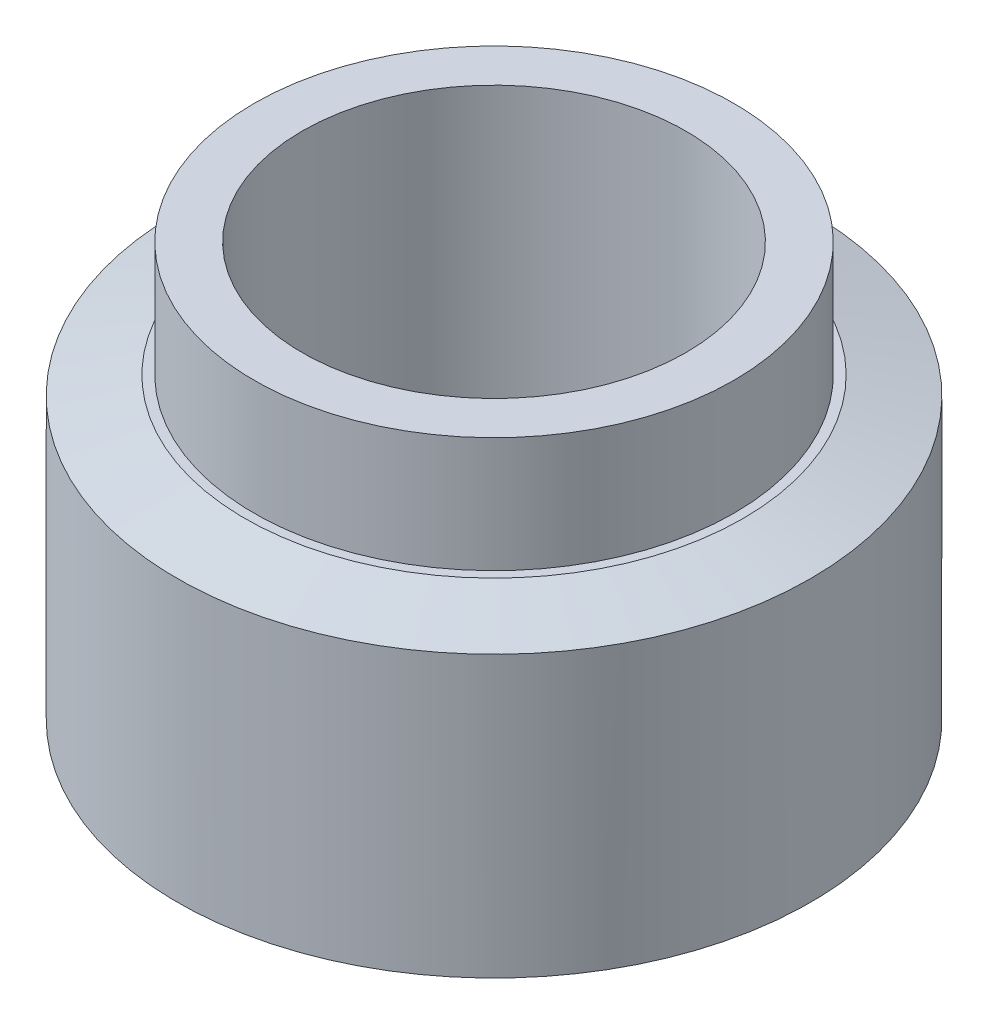
SolidWorks part; units mm, degrees
material "Сталь ШХ15 ГОСТ 801-78"
ref_plane "Plane1" through (0, 0, 0) normal (0, 0, 1) x (1, 0, 0)
ref_plane "Plane2" through (0, 0, 0) normal (0, 1, 0) x (1, 0, 0)
ref_plane "Plane3" through (0, 0, 0) normal (1, 0, 0) x (0, 0, -1)
sketch "Эскиз2" plane through (0, 0, 0) normal (0, 0, 1) x (1, 0, 0)
  line L0 (0, 0) -> (3.3, 0)
  line L1 (3.3, 0) -> (3.3, 3.3)
  line L2 (3.3, 3.3) -> (2.5, 3.3)
  line L3 (2.5, 3.3) -> (2.5, 4.5)
  line L4 (2.5, 4.5) -> (0, 4.5)
  line L5 (0, 4.5) -> (0, 0)
  dimension "D1" = 3.3
  dimension "D2" = 3.3
  dimension "D3" = 1.2
  dimension "D4" = 2.5
ref_axis "Ось1" through (0, 4.5, 0) along (0, -1, 0)
revolve "Повернуть2" add sketch "Эскиз2" angle 360 about axis through (0, 4.5, 0) along (0, -1, 0)
chamfer "Фаска2" distance 0.705 angle 15 1 edges at (-3.3, 3.3, 0) first distance on face at (-2.5, 3.3, 0)
chamfer "Фаска3" distance 0.705 angle 15 1 edges at (-3.3, 0, 0) first distance on face at (-3.3, 0, 0)
sketch "Эскиз4" plane through (0, 4.5, 0) normal (0, 1, 0) x (1, 0, 0)
  circle A0 centre (0, 0) radius 2
  dimension "D1" = 4
extrude "Вырез-Вытянуть2" cut sketch "Эскиз4" against normal through all both contours A0
